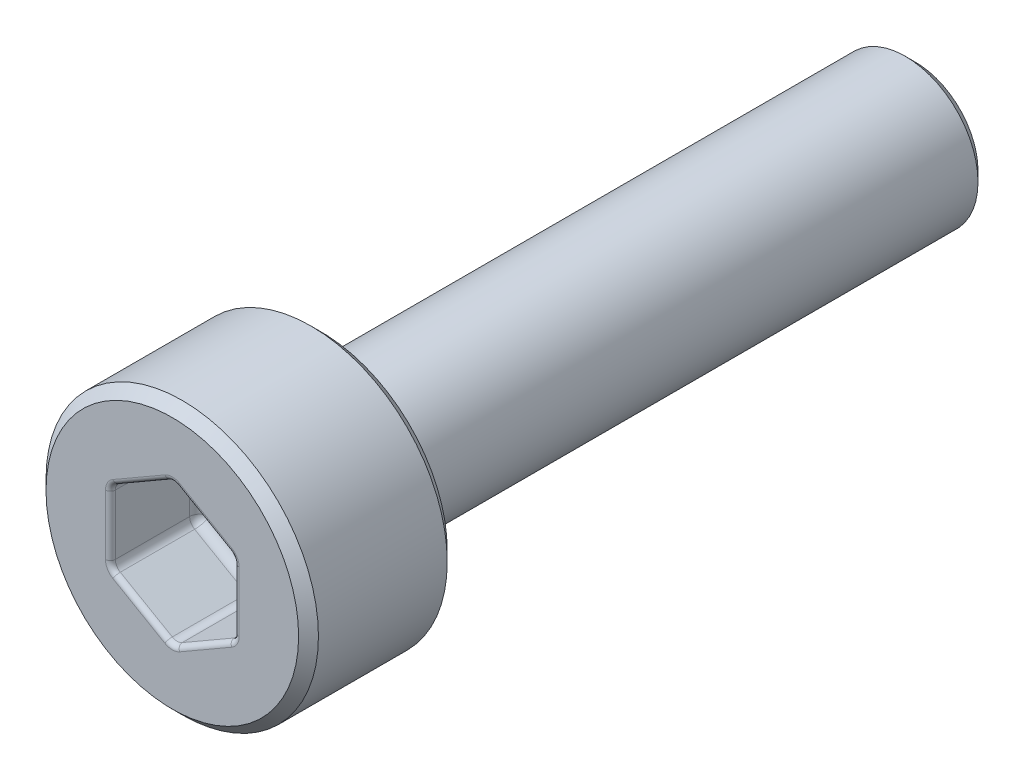
SolidWorks part; units mm, degrees
material "1.4000 (X6Cr13)"
ref_plane "Ebene vorne" through (0, 0, 0) normal (0, 0, 1) x (1, 0, 0)
ref_plane "Ebene oben" through (0, 0, 0) normal (0, 1, 0) x (1, 0, 0)
ref_plane "Ebene rechts" through (0, 0, 0) normal (1, 0, 0) x (0, 0, -1)
sketch "Skizze1" plane through (0, 0, 0) normal (1, 0, 0) x (0, 0, -1)
  line L0 (-21.9199, 0) -> (33.7608, 0) construction
  line L1 (0, 13.9907) -> (0, -9.4798) construction
  line L2 (-3, 0) -> (-3, 2.75)
  line L3 (-3, 2.75) -> (0, 2.75)
  line L4 (0, 2.75) -> (0, 1.465)
  line L5 (0, 1.465) -> (12, 1.465)
  line L6 (12, 1.465) -> (12, 0)
  line L7 (12, 0) -> (-3, 0)
  dimension "D1" = 2.93
  dimension "D2" = 3
  dimension "D3" = 5.5
  dimension "D4" = 12
revolve "Rotation1" add sketch "Skizze1" angle 360 about L0
sketch "Skizze2" plane through (0, 0, 3) normal (0, 0, 1) x (1, 0, 0)
  line L0 (0, 8.6995) -> (0, -7.3778) construction
  line L1 (1.25, -0.7217) -> (1.25, 0.7217)
  line L2 (1.25, 0.7217) -> (0, 1.4434)
  line L3 (0, 1.4434) -> (-1.25, 0.7217)
  line L4 (-1.25, 0.7217) -> (-1.25, -0.7217)
  line L5 (-1.25, -0.7217) -> (0, -1.4434)
  line L6 (0, -1.4434) -> (1.25, -0.7217)
  circle A0 centre (0, 0) radius 1.25 construction
  dimension "D1" = 2.5
extrude "Schnitt-Linear austragen1" cut sketch "Skizze2" against normal blind 1.8
chamfer "Fase1" distance 0.2 angle 45 3 edges at (2.75, 0, 3) (2.75, 0, 0) (1.465, 0, -12)
fillet "Verrundung1" radius 0.2 13 edges at (-0.625, -1.0825, 1.2) (-1.25, 0, 1.2) (-0.625, 1.0825, 1.2) (0.625, 1.0825, 1.2) (1.25, 0, 1.2) (0.625, -1.0825, 1.2) (-1.25, -0.7217, 2.1) (0, -1.4434, 2.1) (1.25, -0.7217, 2.1) (1.25, 0.7217, 2.1) (0, 1.4434, 2.1) (-1.25, 0.7217, 2.1) (1.465, 0, 0)
fillet "Verrundung2" radius 0.1 12 edges at (1.2232, -0.7062, 3) (0.625, -1.0825, 3) (0, -1.4124, 3) (-0.625, -1.0825, 3) (-1.2232, -0.7062, 3) (-1.25, 0, 3) (-1.2232, 0.7062, 3) (-0.625, 1.0825, 3) (0, 1.4124, 3) (0.625, 1.0825, 3) (1.2232, 0.7062, 3) (1.25, 0, 3)
ref_axis "Achse1" through (0, 0, -19.6323) along (0, 0, 1)
